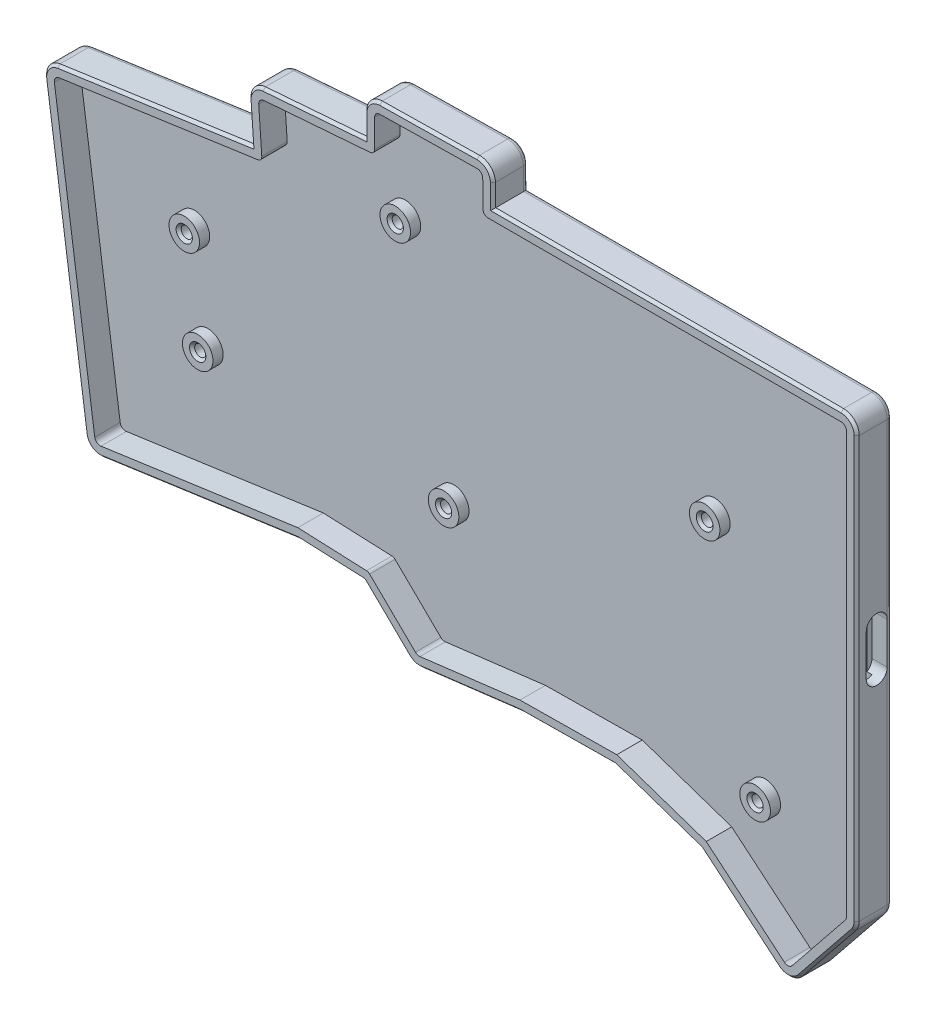
SolidWorks part; units mm, degrees
ref_plane "Front Plane" through (0, 0, 0) normal (0, 0, 1) x (1, 0, 0)
ref_plane "Top Plane" through (0, 0, 0) normal (0, 1, 0) x (1, 0, 0)
ref_plane "Right Plane" through (0, 0, 0) normal (1, 0, 0) x (0, 0, -1)
sketch "Sketch3" plane through (0, 0, 0) normal (0, 0, 1) x (1, 0, 0)
  line L0 (85.1833, 97.7805) -> (154.5968, 97.7805)
  line L1 (155.6718, 96.7055) -> (155.6718, 14.0578)
  line L2 (155.4344, 13.384) -> (144.9894, 0.4011)
  line L3 (143.4619, 0.2505) -> (128.1082, 13.0973)
  line L4 (128.1082, 13.0973) -> (143.4619, 0.2505)
  line L5 (128.1082, 13.0973) -> (110.5249, 19.0829)
  line L6 (110.5249, 19.0829) -> (91.5019, 18.8692)
  line L7 (91.5019, 18.8692) -> (71.8411, 16.4484)
  line L8 (70.9583, 16.7466) -> (61.9589, 25.5411)
  line L9 (70.9583, 16.7466) -> (61.9589, 25.5411)
  line L10 (61.3523, 25.8037) -> (47.8521, 26.3837)
  line L11 (47.8521, 26.3837) -> (9.158, 20.9127)
  line L12 (7.9428, 21.8276) -> (0.0098, 78.274)
  line L13 (0.9224, 79.4879) -> (39.9728, 85.0637)
  line L14 (40.7648, 86.0439) -> (40.1665, 94.5997)
  line L15 (41.1563, 95.7465) -> (62.0679, 97.3591)
  line L16 (62.9218, 98.2813) -> (62.9218, 103.7219)
  line L17 (63.979, 104.7967) -> (83.0927, 105.1138)
  line L18 (84.1855, 104.0536) -> (84.2584, 98.6929)
  line L19 (61.2805, 24.8059) -> (47.901, 25.3807)
  line L20 (47.901, 25.3807) -> (9.298, 19.9225)
  line L21 (6.9525, 21.6885) -> (-0.9804, 78.1349)
  line L22 (0.7811, 80.4778) -> (39.7624, 86.0438)
  line L23 (39.7624, 86.0438) -> (39.169, 94.5299)
  line L24 (41.0794, 96.7436) -> (61.9218, 98.3508)
  line L25 (61.9218, 98.3508) -> (61.9218, 103.7219)
  line L26 (63.9624, 105.7966) -> (83.0761, 106.1137)
  line L27 (85.1854, 104.0671) -> (85.2573, 98.7805)
  line L28 (85.2573, 98.7805) -> (154.5968, 98.7805)
  line L29 (156.6718, 96.7055) -> (156.6718, 14.0578)
  line L30 (156.2136, 12.7572) -> (145.7685, -0.2258)
  line L31 (142.8202, -0.5165) -> (127.6095, 12.2107)
  line L32 (127.6095, 12.2107) -> (110.3649, 18.081)
  line L33 (110.3649, 18.081) -> (91.5689, 17.8699)
  line L34 (91.5689, 17.8699) -> (71.9634, 15.4559)
  line L35 (70.2594, 16.0314) -> (61.2805, 24.8059)
  line L36 (60.8552, 23.8232) -> (47.95, 24.3777)
  line L37 (47.95, 24.3777) -> (9.438, 18.9324)
  line L38 (5.9622, 21.5493) -> (-1.9707, 77.9957)
  line L39 (0.6397, 81.4678) -> (38.6999, 86.9022)
  line L40 (38.6999, 86.9022) -> (38.1714, 94.4602)
  line L41 (41.0025, 97.7406) -> (60.9218, 99.2767)
  line L42 (60.9218, 99.2767) -> (60.9218, 103.7219)
  line L43 (63.9458, 106.7965) -> (83.0596, 107.1135)
  line L44 (86.1853, 104.0807) -> (86.2438, 99.7805)
  line L45 (86.2438, 99.7805) -> (154.5968, 99.7805)
  line L46 (157.6718, 96.7055) -> (157.6718, 14.0578)
  line L47 (156.9927, 12.1304) -> (146.5477, -0.8526)
  line L48 (142.1785, -1.2834) -> (127.1108, 11.3241)
  line L49 (127.1108, 11.3241) -> (110.2048, 17.0791)
  line L50 (110.2048, 17.0791) -> (91.6358, 16.8706)
  line L51 (91.6358, 16.8706) -> (72.0856, 14.4634)
  line L52 (69.5605, 15.3162) -> (60.8552, 23.8232)
  arc A0 (154.5968, 97.7805) -> (155.6718, 96.7055) centre (154.5968, 96.7055) cw
  arc A1 (155.6718, 14.0578) -> (155.4344, 13.384) centre (154.597, 14.0578) cw
  arc A2 (144.9894, 0.4011) -> (143.4619, 0.2505) centre (144.1518, 1.0749) cw
  arc A3 (71.8411, 16.4484) -> (70.9583, 16.7466) centre (71.7098, 17.5155) cw
  arc A4 (61.9589, 25.5411) -> (61.3523, 25.8037) centre (61.3124, 24.8796) ccw
  arc A5 (9.158, 20.9127) -> (7.9428, 21.8276) centre (9.0075, 21.9773) cw
  arc A6 (0.0098, 78.274) -> (0.9224, 79.4879) centre (1.0744, 78.4236) cw
  arc A7 (39.9728, 85.0637) -> (40.7648, 86.0439) centre (39.8421, 85.9794) ccw
  arc A8 (40.1665, 94.5997) -> (41.1563, 95.7465) centre (41.2389, 94.6747) cw
  arc A9 (62.0679, 97.3591) -> (62.9218, 98.2813) centre (61.9968, 98.2814) ccw
  arc A10 (62.9218, 103.7219) -> (63.979, 104.7967) centre (63.9968, 103.7219) cw
  arc A11 (83.0927, 105.1138) -> (84.1855, 104.0536) centre (83.1106, 104.0389) cw
  arc A12 (84.2584, 98.6929) -> (85.1833, 97.7805) centre (85.1833, 98.7055) ccw
  circle A13 centre (22.5341, 62.2507) radius 1.1001
  circle A14 centre (25.1783, 43.4356) radius 1.1001
  circle A15 centre (63.9968, 84.7054) radius 1.1001
  circle A16 centre (73.4968, 41.0054) radius 1.1001
  circle A17 centre (124.7968, 64.4055) radius 1.1454
  circle A18 centre (134.7093, 21.5464) radius 1.1001
  arc A19 (61.2805, 24.8059) -> (61.2805, 24.8059) centre (61.2805, 24.8059) ccw
  arc A20 (9.298, 19.9225) -> (6.9525, 21.6885) centre (9.0075, 21.9773) cw
  arc A21 (-0.9804, 78.1349) -> (0.7811, 80.4778) centre (1.0744, 78.4236) cw
  arc A22 (39.7624, 86.0438) -> (39.7624, 86.0438) centre (39.7624, 86.0438) ccw
  arc A23 (39.169, 94.5299) -> (41.0794, 96.7436) centre (41.2389, 94.6747) cw
  arc A24 (61.9218, 98.3508) -> (61.9218, 98.3508) centre (61.9218, 98.3508) ccw
  arc A25 (61.9218, 103.7219) -> (63.9624, 105.7966) centre (63.9968, 103.7219) cw
  arc A26 (83.0761, 106.1137) -> (85.1854, 104.0671) centre (83.1106, 104.0389) cw
  arc A27 (85.2573, 98.7805) -> (85.2573, 98.7805) centre (85.2573, 98.7805) ccw
  arc A28 (154.5968, 98.7805) -> (156.6718, 96.7055) centre (154.5968, 96.7055) cw
  arc A29 (156.6718, 14.0578) -> (156.2136, 12.7572) centre (154.597, 14.0578) cw
  arc A30 (145.7685, -0.2258) -> (142.8202, -0.5165) centre (144.1518, 1.0749) cw
  arc A31 (71.9634, 15.4559) -> (70.2594, 16.0314) centre (71.7098, 17.5155) cw
  arc A32 (9.438, 18.9324) -> (5.9622, 21.5493) centre (9.0075, 21.9773) cw
  arc A33 (-1.9707, 77.9957) -> (0.6397, 81.4678) centre (1.0744, 78.4236) cw
  arc A34 (38.6999, 86.9022) -> (38.6999, 86.9022) centre (38.6999, 86.9022) ccw
  arc A35 (38.1714, 94.4602) -> (41.0025, 97.7406) centre (41.2389, 94.6747) cw
  arc A36 (60.9218, 99.2767) -> (60.9218, 99.2767) centre (60.9218, 99.2767) ccw
  arc A37 (60.9218, 103.7219) -> (63.9458, 106.7965) centre (63.9968, 103.7219) cw
  arc A38 (83.0596, 107.1135) -> (86.1853, 104.0807) centre (83.1106, 104.0389) cw
  arc A39 (86.2438, 99.7805) -> (86.2438, 99.7805) centre (86.2438, 99.7805) ccw
  arc A40 (154.5968, 99.7805) -> (157.6718, 96.7055) centre (154.5968, 96.7055) cw
  arc A41 (157.6718, 14.0578) -> (156.9927, 12.1304) centre (154.597, 14.0578) cw
  arc A42 (146.5477, -0.8526) -> (142.1785, -1.2834) centre (144.1518, 1.0749) cw
  arc A43 (72.0856, 14.4634) -> (69.5605, 15.3162) centre (71.7098, 17.5155) cw
  arc A44 (60.8552, 23.8232) -> (60.8552, 23.8232) centre (60.8552, 23.8232) ccw
  dimension "D1" = 1
  dimension "D2" = 1
extrude "Boss-Extrude1" add sketch "Sketch3" along normal blind 2 contours A43 L51 L50 L49 L48 A42 L47 A41 L46 A40 L45 L44 A38 L43 A37 L42 L41 A35 L40 L39 A33 L38 A32 L37 L36 L52 L34 A31 L35 L19 L20 A20 L21 A21 L22 L23 A23 L24 L25 A25 L26 A26 L27 L28 A28 L29 A29 L30 A30 L31 | A31 L34 L33 L32 L31 A30 L30 A29 L29 A28 L28 L27 A26 L26 A25 L25 L24 A23 L23 L22 A21 L21 A20 L20 L19 L35 L18 A12 L0 A0 L1 A1 L2 A2 L3 L5 L6 L7 A3 L8 A4 L10 L11 A5 L12 A6 L13 A7 L14 A8 | A12 L18 A11 L17 A10 L16 A9 L15 A8 L14 A7 L13 A6 L12 A5 L11 L10 A4 L8 A3 L7 L6 L5 L3 A2 L2 A1 L1 A0 L0 A18 A17 A16 A15 A14 A13 | A13 | A14 | A15 | A16 | A17 | A18 region at (85.6931, 56.8689, 0) region at (54.5989, 25.2837, 0) region at (54.4109, 24.2937, 0) region at (22.5341, 62.2507, 0) region at (25.1783, 43.4356, 0) region at (63.9968, 84.7054, 0) region at (73.4968, 41.0054, 0) region at (124.7968, 64.4055, 0) region at (134.7093, 21.5464, 0)
sketch "Sketch4" plane through (0, 0, 0) normal (0, 0, 1) x (1, 0, 0)
  line L0 (85.1833, 97.7805) -> (154.5968, 97.7805)
  line L1 (155.6718, 96.7055) -> (155.6718, 14.0578)
  line L2 (155.4344, 13.384) -> (144.9894, 0.4011)
  line L3 (143.4619, 0.2505) -> (128.1082, 13.0973)
  line L4 (128.1082, 13.0973) -> (143.4619, 0.2505)
  line L5 (128.1082, 13.0973) -> (110.5249, 19.0829)
  line L6 (110.5249, 19.0829) -> (91.5019, 18.8692)
  line L7 (91.5019, 18.8692) -> (71.8411, 16.4484)
  line L8 (70.9583, 16.7466) -> (61.9589, 25.5411)
  line L9 (70.9583, 16.7466) -> (61.9589, 25.5411)
  line L10 (61.3523, 25.8037) -> (47.8521, 26.3837)
  line L11 (47.8521, 26.3837) -> (9.158, 20.9127)
  line L12 (7.9428, 21.8276) -> (0.0098, 78.274)
  line L13 (0.9224, 79.4879) -> (39.9728, 85.0637)
  line L14 (40.7648, 86.0439) -> (40.1665, 94.5997)
  line L15 (41.1563, 95.7465) -> (62.0679, 97.3591)
  line L16 (62.9218, 98.2813) -> (62.9218, 103.7219)
  line L17 (63.979, 104.7967) -> (83.0927, 105.1138)
  line L18 (84.1855, 104.0536) -> (84.2584, 98.6929)
  line L19 (61.2805, 24.8059) -> (47.901, 25.3807)
  line L20 (47.901, 25.3807) -> (9.298, 19.9225)
  line L21 (6.9525, 21.6885) -> (-0.9804, 78.1349)
  line L22 (0.7811, 80.4778) -> (39.7624, 86.0438)
  line L23 (39.7624, 86.0438) -> (39.169, 94.5299)
  line L24 (41.0794, 96.7436) -> (61.9218, 98.3508)
  line L25 (61.9218, 98.3508) -> (61.9218, 103.7219)
  line L26 (63.9624, 105.7966) -> (83.0761, 106.1137)
  line L27 (85.1854, 104.0671) -> (85.2573, 98.7805)
  line L28 (85.2573, 98.7805) -> (154.5968, 98.7805)
  line L29 (156.6718, 96.7055) -> (156.6718, 14.0578)
  line L30 (156.2136, 12.7572) -> (145.7685, -0.2258)
  line L31 (142.8202, -0.5165) -> (127.6095, 12.2107)
  line L32 (127.6095, 12.2107) -> (110.3649, 18.081)
  line L33 (110.3649, 18.081) -> (91.5689, 17.8699)
  line L34 (91.5689, 17.8699) -> (71.9634, 15.4559)
  line L35 (70.2594, 16.0314) -> (61.2805, 24.8059)
  line L36 (60.8552, 23.8232) -> (47.95, 24.3777)
  line L37 (47.95, 24.3777) -> (9.438, 18.9324)
  line L38 (5.9622, 21.5493) -> (-1.9707, 77.9957)
  line L39 (0.6397, 81.4678) -> (38.6999, 86.9022)
  line L40 (38.6999, 86.9022) -> (38.1714, 94.4602)
  line L41 (41.0025, 97.7406) -> (60.9218, 99.2767)
  line L42 (60.9218, 99.2767) -> (60.9218, 103.7219)
  line L43 (63.9458, 106.7965) -> (83.0596, 107.1135)
  line L44 (86.1853, 104.0807) -> (86.2438, 99.7805)
  line L45 (86.2438, 99.7805) -> (154.5968, 99.7805)
  line L46 (157.6718, 96.7055) -> (157.6718, 14.0578)
  line L47 (156.9927, 12.1304) -> (146.5477, -0.8526)
  line L48 (142.1785, -1.2834) -> (127.1108, 11.3241)
  line L49 (127.1108, 11.3241) -> (110.2048, 17.0791)
  line L50 (110.2048, 17.0791) -> (91.6358, 16.8706)
  line L51 (91.6358, 16.8706) -> (72.0856, 14.4634)
  line L52 (69.5605, 15.3162) -> (60.8552, 23.8232)
  arc A0 (154.5968, 97.7805) -> (155.6718, 96.7055) centre (154.5968, 96.7055) cw
  arc A1 (155.6718, 14.0578) -> (155.4344, 13.384) centre (154.597, 14.0578) cw
  arc A2 (144.9894, 0.4011) -> (143.4619, 0.2505) centre (144.1518, 1.0749) cw
  arc A3 (71.8411, 16.4484) -> (70.9583, 16.7466) centre (71.7098, 17.5155) cw
  arc A4 (61.9589, 25.5411) -> (61.3523, 25.8037) centre (61.3124, 24.8796) ccw
  arc A5 (9.158, 20.9127) -> (7.9428, 21.8276) centre (9.0075, 21.9773) cw
  arc A6 (0.0098, 78.274) -> (0.9224, 79.4879) centre (1.0744, 78.4236) cw
  arc A7 (39.9728, 85.0637) -> (40.7648, 86.0439) centre (39.8421, 85.9794) ccw
  arc A8 (40.1665, 94.5997) -> (41.1563, 95.7465) centre (41.2389, 94.6747) cw
  arc A9 (62.0679, 97.3591) -> (62.9218, 98.2813) centre (61.9968, 98.2814) ccw
  arc A10 (62.9218, 103.7219) -> (63.979, 104.7967) centre (63.9968, 103.7219) cw
  arc A11 (83.0927, 105.1138) -> (84.1855, 104.0536) centre (83.1106, 104.0389) cw
  arc A12 (84.2584, 98.6929) -> (85.1833, 97.7805) centre (85.1833, 98.7055) ccw
  circle A13 centre (22.5341, 62.2507) radius 1.1001
  circle A14 centre (25.1783, 43.4356) radius 1.1001
  circle A15 centre (63.9968, 84.7054) radius 1.1001
  circle A16 centre (73.4968, 41.0054) radius 1.1001
  circle A17 centre (124.7968, 64.4055) radius 1.1454
  circle A18 centre (134.7093, 21.5464) radius 1.1001
  arc A19 (61.2805, 24.8059) -> (61.2805, 24.8059) centre (61.2805, 24.8059) ccw
  arc A20 (9.298, 19.9225) -> (6.9525, 21.6885) centre (9.0075, 21.9773) cw
  arc A21 (-0.9804, 78.1349) -> (0.7811, 80.4778) centre (1.0744, 78.4236) cw
  arc A22 (39.7624, 86.0438) -> (39.7624, 86.0438) centre (39.7624, 86.0438) ccw
  arc A23 (39.169, 94.5299) -> (41.0794, 96.7436) centre (41.2389, 94.6747) cw
  arc A24 (61.9218, 98.3508) -> (61.9218, 98.3508) centre (61.9218, 98.3508) ccw
  arc A25 (61.9218, 103.7219) -> (63.9624, 105.7966) centre (63.9968, 103.7219) cw
  arc A26 (83.0761, 106.1137) -> (85.1854, 104.0671) centre (83.1106, 104.0389) cw
  arc A27 (85.2573, 98.7805) -> (85.2573, 98.7805) centre (85.2573, 98.7805) ccw
  arc A28 (154.5968, 98.7805) -> (156.6718, 96.7055) centre (154.5968, 96.7055) cw
  arc A29 (156.6718, 14.0578) -> (156.2136, 12.7572) centre (154.597, 14.0578) cw
  arc A30 (145.7685, -0.2258) -> (142.8202, -0.5165) centre (144.1518, 1.0749) cw
  arc A31 (71.9634, 15.4559) -> (70.2594, 16.0314) centre (71.7098, 17.5155) cw
  arc A32 (9.438, 18.9324) -> (5.9622, 21.5493) centre (9.0075, 21.9773) cw
  arc A33 (-1.9707, 77.9957) -> (0.6397, 81.4678) centre (1.0744, 78.4236) cw
  arc A34 (38.6999, 86.9022) -> (38.6999, 86.9022) centre (38.6999, 86.9022) ccw
  arc A35 (38.1714, 94.4602) -> (41.0025, 97.7406) centre (41.2389, 94.6747) cw
  arc A36 (60.9218, 99.2767) -> (60.9218, 99.2767) centre (60.9218, 99.2767) ccw
  arc A37 (60.9218, 103.7219) -> (63.9458, 106.7965) centre (63.9968, 103.7219) cw
  arc A38 (83.0596, 107.1135) -> (86.1853, 104.0807) centre (83.1106, 104.0389) cw
  arc A39 (86.2438, 99.7805) -> (86.2438, 99.7805) centre (86.2438, 99.7805) ccw
  arc A40 (154.5968, 99.7805) -> (157.6718, 96.7055) centre (154.5968, 96.7055) cw
  arc A41 (157.6718, 14.0578) -> (156.9927, 12.1304) centre (154.597, 14.0578) cw
  arc A42 (146.5477, -0.8526) -> (142.1785, -1.2834) centre (144.1518, 1.0749) cw
  arc A43 (72.0856, 14.4634) -> (69.5605, 15.3162) centre (71.7098, 17.5155) cw
  arc A44 (60.8552, 23.8232) -> (60.8552, 23.8232) centre (60.8552, 23.8232) ccw
  dimension "D1" = 1
  dimension "D2" = 1
extrude "Boss-Extrude2" add sketch "Sketch4" along normal blind 7 contours A43 L51 L50 L49 L48 A42 L47 A41 L46 A40 L45 L44 A38 L43 A37 L42 L41 A35 L40 L39 A33 L38 A32 L37 L36 L52 L34 A31 L35 L19 L20 A20 L21 A21 L22 L23 A23 L24 L25 A25 L26 A26 L27 L28 A28 L29 A29 L30 A30 L31 | A31 L34 L33 L32 L31 A30 L30 A29 L29 A28 L28 L27 A26 L26 A25 L25 L24 A23 L23 L22 A21 L21 A20 L20 L19 L35 L18 A12 L0 A0 L1 A1 L2 A2 L3 L5 L6 L7 A3 L8 A4 L10 L11 A5 L12 A6 L13 A7 L14 A8 region at (54.5989, 25.2837, 0) region at (54.4109, 24.2937, 0)
sketch "Sketch7" plane through (0, 0, 0) normal (0, 0, 1) x (1, 0, 0)
  circle A0 centre (25.1783, 43.4356) radius 3
  circle A1 centre (22.5341, 62.2507) radius 3
  circle A2 centre (63.9968, 84.7054) radius 3
  circle A3 centre (73.4968, 41.0054) radius 3
  circle A4 centre (124.7968, 64.4055) radius 3
  circle A5 centre (134.7093, 21.5464) radius 3
  circle A13 centre (22.5341, 62.2507) radius 1.1001
  circle A14 centre (25.1783, 43.4356) radius 1.1001
  circle A15 centre (63.9968, 84.7054) radius 1.1001
  circle A16 centre (73.4968, 41.0054) radius 1.1001
  circle A17 centre (124.7968, 64.4055) radius 1.1454
  circle A18 centre (134.7093, 21.5464) radius 1.1001
  dimension "D1" = 6
  dimension "D2" = 6
  dimension "D3" = 6
  dimension "D4" = 6
  dimension "D5" = 6
  dimension "D6" = 6
extrude "Boss-Extrude3" add sketch "Sketch7" along normal blind 4
sketch "Sketch8" plane through (157.6718, 0, 0) normal (1, 0, 0) x (0, 0, -1)
  line L0 (0, 96.7055) -> (0, 14.0578) construction
  line L5 (-3.0616, 62.6695) -> (-3.0616, 54.5415) construction
  line L6 (-1, 62.6695) -> (-1, 54.5415)
  line L7 (-5.1232, 62.6695) -> (-5.1232, 54.5415)
  line L8 (-7, 96.7055) -> (0, 96.7055) construction
  arc A0 (-1, 62.6695) -> (-5.1232, 62.6695) centre (-3.0616, 62.6695) ccw
  arc A1 (-5.1232, 54.5415) -> (-1, 54.5415) centre (-3.0616, 54.5415) ccw
  point P8 (-3.0616, 58.6055)
  dimension "D1" = 8.128
  dimension "D2" = 1
  dimension "D3" = 34.036
extrude "Cut-Extrude1" cut sketch "Sketch8" against normal blind 3
fillet "Fillet2" radius 1 26 edges at (81.8607, 15.667, 0) (100.9203, 16.9749, 0) (118.6578, 14.2016, 0) (134.6446, 5.0203, 0) (144.4535, -1.9852, 0) (151.7702, 5.6389, 0) (157.4971, 13.036, 0) (157.6718, 55.3816, 0) (156.7712, 98.8798, 0) (120.4203, 99.7805, 0) (86.2145, 101.9306, 0) (85.2519, 106.2459, 0) (73.5027, 106.955, 0) (61.8045, 105.8781, 0) (60.9218, 101.4993, 0) (50.9622, 98.5086, 0) (38.911, 96.6838, 0) (38.4356, 90.6812, 0) (54.4026, 24.1004, 0) (65.2079, 19.5697, 0) (70.7258, 14.602, 0) (19.6698, 84.185, 0) (-1.3835, 80.2715, 0) (1.9958, 49.7725, 0) (7.1578, 19.5206, 0) (28.694, 21.655, 0)
chamfer "Chamfer1" distance 0.5 angle 45 26 edges at (65.2079, 19.5697, 7) (54.4026, 24.1004, 7) (70.7258, 14.602, 7) (81.8607, 15.667, 7) (100.9203, 16.9749, 7) (118.6578, 14.2016, 7) (134.6446, 5.0203, 7) (144.4535, -1.9852, 7) (151.7702, 5.6389, 7) (157.4971, 13.036, 7) (157.6718, 55.3816, 7) (156.7712, 98.8798, 7) (120.4203, 99.7805, 7) (86.2145, 101.9306, 7) (85.2519, 106.2459, 7) (73.5027, 106.955, 7) (61.8045, 105.8781, 7) (60.9218, 101.4993, 7) (50.9622, 98.5086, 7) (38.911, 96.6838, 7) (38.4356, 90.6812, 7) (19.6698, 84.185, 7) (-1.3835, 80.2715, 7) (1.9958, 49.7725, 7) (7.1578, 19.5206, 7) (28.694, 21.655, 7)
chamfer "Chamfer2" distance 0.5 angle 45 6 edges at (26.2784, 43.4356, 4) (74.5969, 41.0054, 4) (135.8094, 21.5464, 4) (125.9422, 64.4055, 4) (65.0969, 84.7054, 4) (23.6341, 62.2507, 4)
